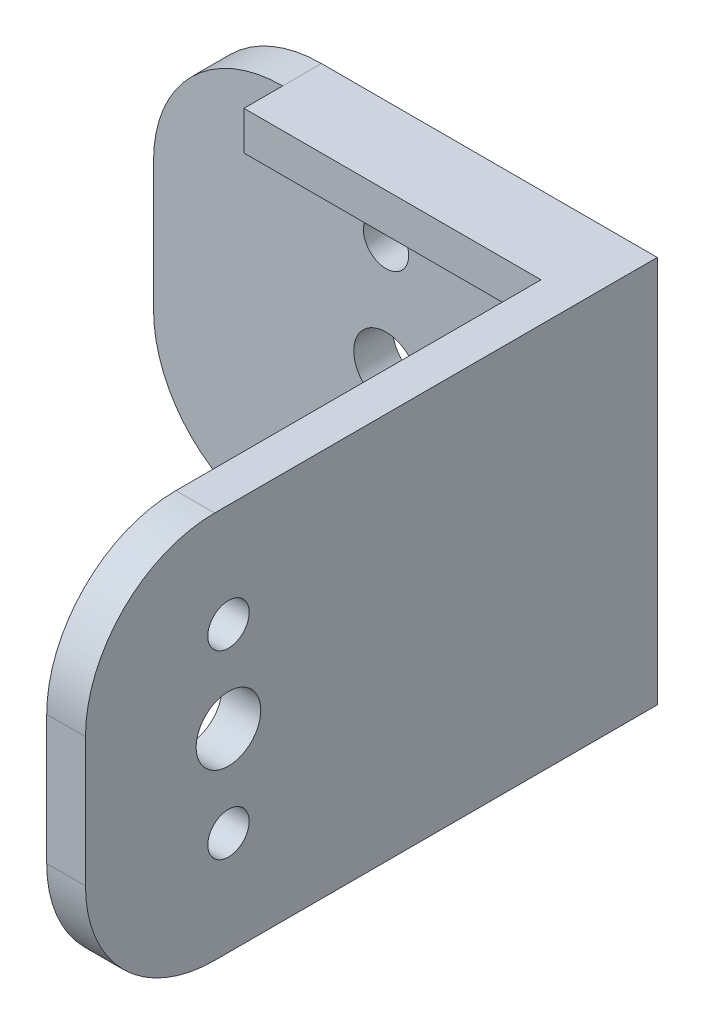
SolidWorks part; units mm, degrees
material "Plastique personnalisé"
ref_plane "Plan de face" through (0, 0, 0) normal (0, 0, 1) x (1, 0, 0)
ref_plane "Plan de dessus" through (0, 0, 0) normal (0, 1, 0) x (1, 0, 0)
ref_plane "Plan de droite" through (0, 0, 0) normal (1, 0, 0) x (0, 0, -1)
sketch "Esquisse1" plane through (0, 0, 0) normal (0, 0, 1) x (1, 0, 0)
  line L0 (3, 30) -> (3, 0)
  line L1 (0, 0) -> (36, 0)
  line L2 (0, 0) -> (0, 30)
  line L3 (0, 30) -> (36, 30)
  line L4 (36, 0) -> (36, 30)
  line L5 (33, 30) -> (33, 0)
  dimension "D1" = 36
  dimension "D2" = 3
  dimension "20" = 30
  dimension "D3" = 3
extrude "Boss.-Extru.1" add sketch "Esquisse1" along normal blind 41.27 contours L3 L5 L1 L4 region at (34.5, 15, 0)
extrude "Boss.-Extru.2" add sketch "Esquisse1<3>" against normal blind 3 contours L3 L4 L1 L2
sketch "Esquisse1<3>" plane through (0, 0, 0) normal (0, 0, 1) x (1, 0, 0) same geometry as "Esquisse1"
sketch "Esquisse3" plane through (36, 0, 0) normal (1, 0, 0) x (0, 0, -1)
  line L0 (-41.27, 15) -> (3, 15) construction
  line L1 (-41.27, 0) -> (-41.27, 30) construction
  line L2 (3, 0) -> (3, 30) construction
  line L8 (-30.1979, 15) -> (-30.1979, 18.5318) construction
  line L9 (-30.1979, 15) -> (-30.1979, 1.2804) construction
  circle A1 centre (-30.1979, 15) radius 2.5
  circle A2 centre (-30.1979, 22) radius 1.6
  circle A5 centre (-30.1979, 8) radius 1.6
  circle A7 centre (-37.1979, 15) radius 1.6 [skipped]
  circle A8 centre (-23.1979, 15) radius 1.6 [skipped]
  dimension "D1" = 11.0721
  dimension "D2" = 5
  dimension "D4" = 3.2
  dimension "D5" = 7
  dimension "D7" = 4
extrude "Enlèv. mat.-Extru.2" cut sketch "Esquisse3" against normal blind 85 contours A2 | A5 | A1 region at (36, 22, 30.1979) region at (36, 8, 30.1979)
fillet "Congé2" radius 2 1 edges at (33, 15, 0)
sketch "Esquisse7" plane through (0, 0, -3) normal (0, 0, -1) x (-1, 0, 0)
  line L0 (-36, 15) -> (0, 15) construction
  line L1 (-36, 0) -> (-36, 30) construction
  line L2 (0, 0) -> (0, 30) construction
  line L3 (-18, 15) -> (-18, 8.6257) construction
  line L4 (-18, 15) -> (-18, -8.6257) construction
  circle A3 centre (-18, 15) radius 2.5
  circle A4 centre (-18, 23.5) radius 1.75
  circle A11 centre (-18, 6.5) radius 1.75
  circle A13 centre (-9.5, 15) radius 1.75 [skipped]
  circle A14 centre (-26.5, 15) radius 1.75 [skipped]
  point P6 (-18, 15)
  dimension "D1" = 5
  dimension "D3" = 3.5
  dimension "D4" = 8.5
  dimension "D6" = 4
fillet "Congé3" radius 10 4 edges at (0, 30, -1.5) (0, 0, -1.5) (34.5, 30, 41.27) (34.5, 0, 41.27)
extrude "Enlèv. mat.-Extru.3" cut sketch "Esquisse7" against normal blind 10 contours A4 | A11 | A3 region at (18, 23.5, -3) region at (18, 6.5, -3)
sketch "Esquisse8" plane through (0, 0, 0) normal (0, 0, 1) x (1, 0, 0)
  line L0 (33, 30) -> (10, 30)
  line L1 (10, 30) -> (10, 27)
  line L2 (10, 27) -> (33, 27)
  line L3 (33, 30) -> (33, 27)
  line L5 (33, 0) -> (10, 0)
  line L6 (33, 0) -> (33, 3)
  line L7 (33, 3) -> (10, 3)
  line L8 (10, 0) -> (10, 3)
  dimension "D1" = 3
  dimension "D2" = 3
extrude "Boss.-Extru.3" add sketch "Esquisse8" along normal blind 3
